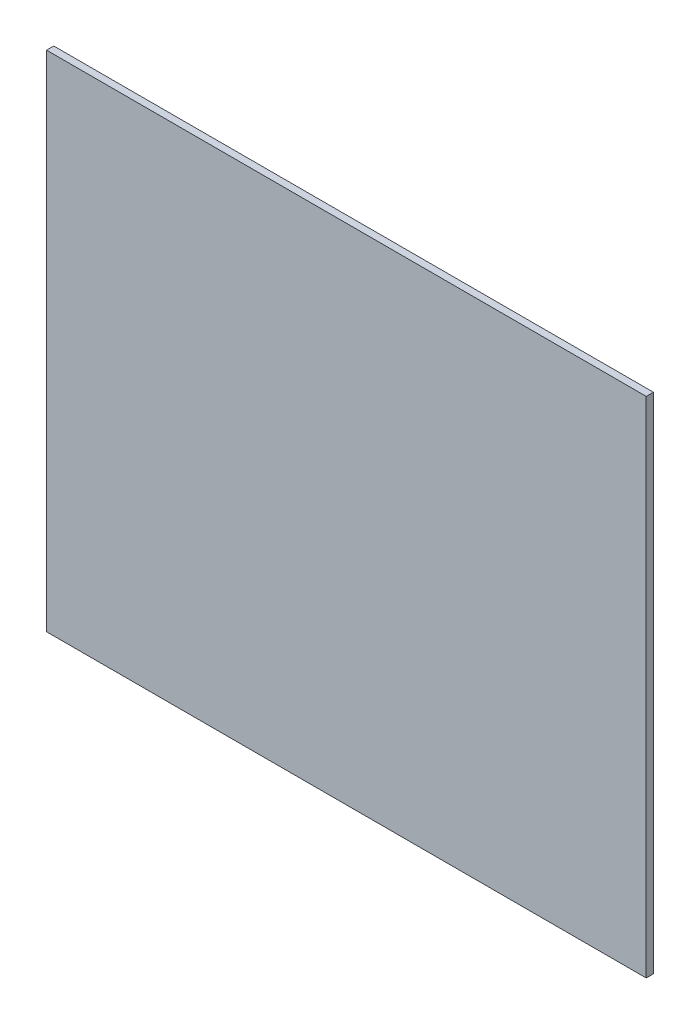
SolidWorks part; units mm, degrees
ref_plane "Ön Düzlem" through (0, 0, 0) normal (0, 0, 1) x (1, 0, 0)
ref_plane "Üst Düzlem" through (0, 0, 0) normal (0, 1, 0) x (1, 0, 0)
ref_plane "Sağ Düzlem" through (0, 0, 0) normal (1, 0, 0) x (0, 0, -1)
sketch "Çizim1" plane through (0, 0, 0) normal (0, 0, 1) x (1, 0, 0)
  line L1 (0, 0) -> (1250, 0)
  line L2 (0, 0) -> (0, -1050)
  line L3 (0, -1050) -> (1250, -1050)
  line L4 (1250, 0) -> (1250, -1050)
  dimension "D1" = 1250
  dimension "D2" = 1050
base flange "Taban-Flanş1" sketch "Çizim1" thickness 15 reverse thickness direction no parameters "D1"=6
sketch "Büküm-Çizgileri1" [suppressed] plane through (0, 0, 0) normal (0, 1, 0) x (1, 0, 0)
sketch "Sınırlandırma-Kutusu1" [suppressed] plane through (0, 0, 0) normal (0, 1, 0) x (1, 0, 0)
sheet metal parameters "Sac-Levha1" thickness 15 parameters "D1"=6
flat pattern "Düz-Çoğaltma1" [suppressed]
sketch "Büküm-Çizgileri2" plane through (0, 0, 0) normal (0, 1, 0) x (1, 0, 0)
sketch3d "Sınırlandırma-Kutusu2" [suppressed]
  line L0 (0, -1050, 0) -> (1250, -1050, 0) construction
  line L1 (0, 0, 0) -> (1250, 0, 0) construction
  line L2 (0, -1050, 0) -> (0, 0, 0) construction
  line L3 (1250, -1050, 0) -> (1250, 0, 0) construction
